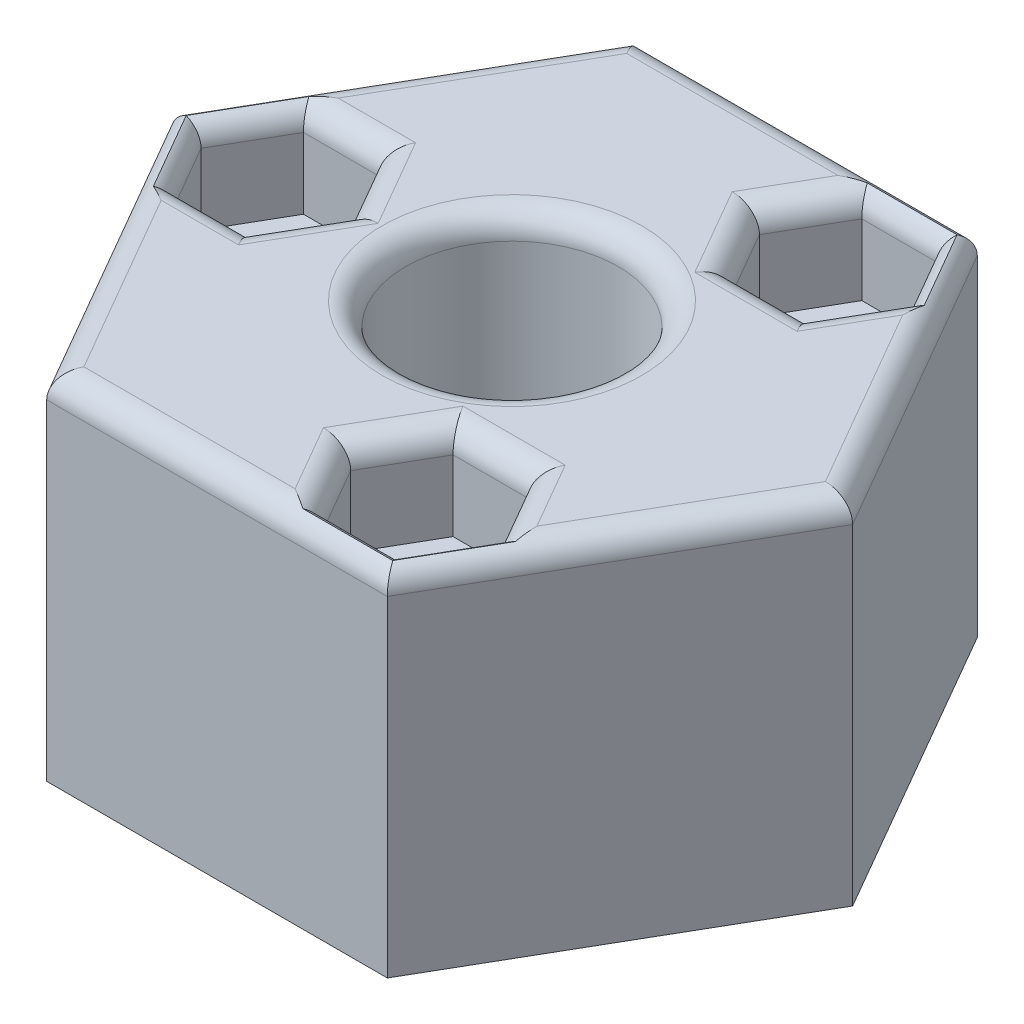
SolidWorks part; units mm, degrees
material "ABS"
ref_plane "Front" through (0, 0, 0) normal (0, 0, 1) x (1, 0, 0)
ref_plane "Top" through (0, 0, 0) normal (0, 1, 0) x (1, 0, 0)
ref_plane "Right" through (0, 0, 0) normal (1, 0, 0) x (0, 0, -1)
sketch "Esquisse1" plane through (0, 0, 0) normal (0, 1, 0) x (1, 0, 0)
  line L1 (6.6, 3.8105) -> (0, 7.621)
  line L2 (0, 7.621) -> (-6.6, 3.8105)
  line L3 (-6.6, 3.8105) -> (-6.6, -3.8105)
  line L4 (-6.6, -3.8105) -> (0, -7.621)
  line L5 (0, -7.621) -> (6.6, -3.8105)
  line L6 (6.6, -3.8105) -> (6.6, 3.8105)
  line L7 (7.2169, 12.5) -> (-7.2169, 12.5)
  line L8 (-7.2169, 12.5) -> (-14.4338, 0)
  line L9 (-14.4338, 0) -> (-7.2169, -12.5)
  line L10 (-7.2169, -12.5) -> (7.2169, -12.5)
  line L11 (7.2169, -12.5) -> (14.4338, 0)
  line L12 (14.4338, 0) -> (7.2169, 12.5)
  circle A1 centre (-10, 0) radius 1.2
  circle A2 centre (5, 8.6603) radius 1.2
  circle A3 centre (5, -8.6603) radius 1.2
  circle A4 centre (0, 0) radius 10 construction
  circle A5 centre (0, 0) radius 6.6 construction
  circle A6 centre (0, 0) radius 12.5 construction
  dimension "D1" = 20
  dimension "D3" = 2.4
  dimension "D2" = 120
  dimension "D4" = 13.2
  dimension "D5" = 25
extrude "Boss.-Extru.1" add sketch "Esquisse1" along normal blind 15
sketch "Esquisse2" plane through (0, 15, 0) normal (0, 1, 0) x (1, 0, 0)
  circle A0 centre (0, 0) radius 7.621
  circle A1 centre (0, 0) radius 4.5
  dimension "D1" = 9
extrude "Boss.-Extru.2" add sketch "Esquisse2" against normal offset from surface (8.2 mm away) 6.8 up to face at (5, 0, 9.8603)
sketch "Esquisse3" plane through (0, 15, 0) normal (0, 1, 0) x (1, 0, 0)
  line L0 (7.2169, 12.5) -> (-7.2169, 12.5) construction
  line L1 (-8.4123, 2.75) -> (-11.5877, 2.75)
  line L2 (-11.5877, 2.75) -> (-13.1754, 0)
  line L3 (-13.1754, 0) -> (-11.5877, -2.75)
  line L4 (-11.5877, -2.75) -> (-8.4123, -2.75)
  line L5 (-8.4123, -2.75) -> (-6.8246, 0)
  line L6 (-6.8246, 0) -> (-8.4123, 2.75)
  line L7 (6.5877, 5.9103) -> (8.1754, 8.6603)
  line L8 (8.1754, 8.6603) -> (6.5877, 11.4103)
  line L9 (6.5877, 11.4103) -> (3.4123, 11.4103)
  line L10 (3.4123, 11.4103) -> (1.8246, 8.6603)
  line L11 (1.8246, 8.6603) -> (3.4123, 5.9103)
  line L12 (3.4123, 5.9103) -> (6.5877, 5.9103)
  line L13 (6.5877, -5.9103) -> (3.4123, -5.9103)
  line L14 (3.4123, -5.9103) -> (1.8246, -8.6603)
  line L15 (1.8246, -8.6603) -> (3.4123, -11.4103)
  line L16 (3.4123, -11.4103) -> (6.5877, -11.4103)
  line L17 (6.5877, -11.4103) -> (8.1754, -8.6603)
  line L18 (8.1754, -8.6603) -> (6.5877, -5.9103)
  circle A0 centre (-10, 0) radius 2.75 construction
  circle A1 centre (5, 8.6603) radius 2.75 construction
  circle A2 centre (5, -8.6603) radius 2.75 construction
  dimension "D1" = 5.5
  dimension "D2" = 1.0897
extrude "Enlèv. mat.-Extru.1" cut sketch "Esquisse3" against normal blind 4
sketch "Esquisse5" plane through (0, 11, 0) normal (0, 1, 0) x (1, 0, 0)
  circle A0 centre (5, 8.6603) radius 1.2 construction
  circle A1 centre (5, -8.6603) radius 1.2 construction
  circle A2 centre (-10, 0) radius 1.2 construction
  circle A3 centre (5, 8.6603) radius 1.2
  circle A4 centre (5, -8.6603) radius 1.2
  circle A5 centre (-10, 0) radius 1.2
extrude "Boss.-Extru.4" [suppressed] add sketch "Esquisse5" against normal blind 0.2
sketch "Esquisse4" plane through (0, 15, 0) normal (0, 1, 0) x (1, 0, 0)
  line L6 (14.4338, 0) -> (7.2169, 12.5)
  line L8 (14.4338, 0) -> (7.2169, 12.5)
  line L10 (7.2169, 12.5) -> (-7.2169, 12.5)
  line L18 (7.2169, 12.5) -> (-7.2169, 12.5)
  line L19 (-7.2169, 12.5) -> (-14.4338, 0)
  line L20 (-7.2169, 12.5) -> (-14.4338, 0)
  line L21 (-14.4338, 0) -> (-7.2169, -12.5)
  line L22 (-14.4338, 0) -> (-7.2169, -12.5)
  line L23 (-7.2169, -12.5) -> (7.2169, -12.5)
  line L24 (-7.2169, -12.5) -> (7.2169, -12.5)
  line L25 (7.2169, -12.5) -> (14.4338, 0)
  line L26 (7.2169, -12.5) -> (14.4338, 0)
  dimension "D1" = 0
extrude "Boss.-Extru.3" [suppressed] add sketch "Esquisse4" against normal blind 0.2
fillet "Congé1" radius 1 25 edges at (10.8253, 15, 6.25) (0, 15, 12.5) (-10.8253, 15, 6.25) (-10.8253, 15, -6.25) (0, 15, -12.5) (10.8253, 15, -6.25) (0, 15, 4.5) (5, 15, 5.9103) (2.6184, 15, 7.2853) (2.6184, 15, 10.0353) (5, 15, 11.4103) (7.3816, 15, 10.0353) (7.3816, 15, 7.2853) (7.3816, 15, -7.2853) (7.3816, 15, -10.0353) (5, 15, -11.4103) (2.6184, 15, -10.0353) (2.6184, 15, -7.2853) (5, 15, -5.9103) (-10, 15, -2.75) (-12.3816, 15, -1.375) (-12.3816, 15, 1.375) (-10, 15, 2.75) (-7.6184, 15, 1.375) (-7.6184, 15, -1.375)
